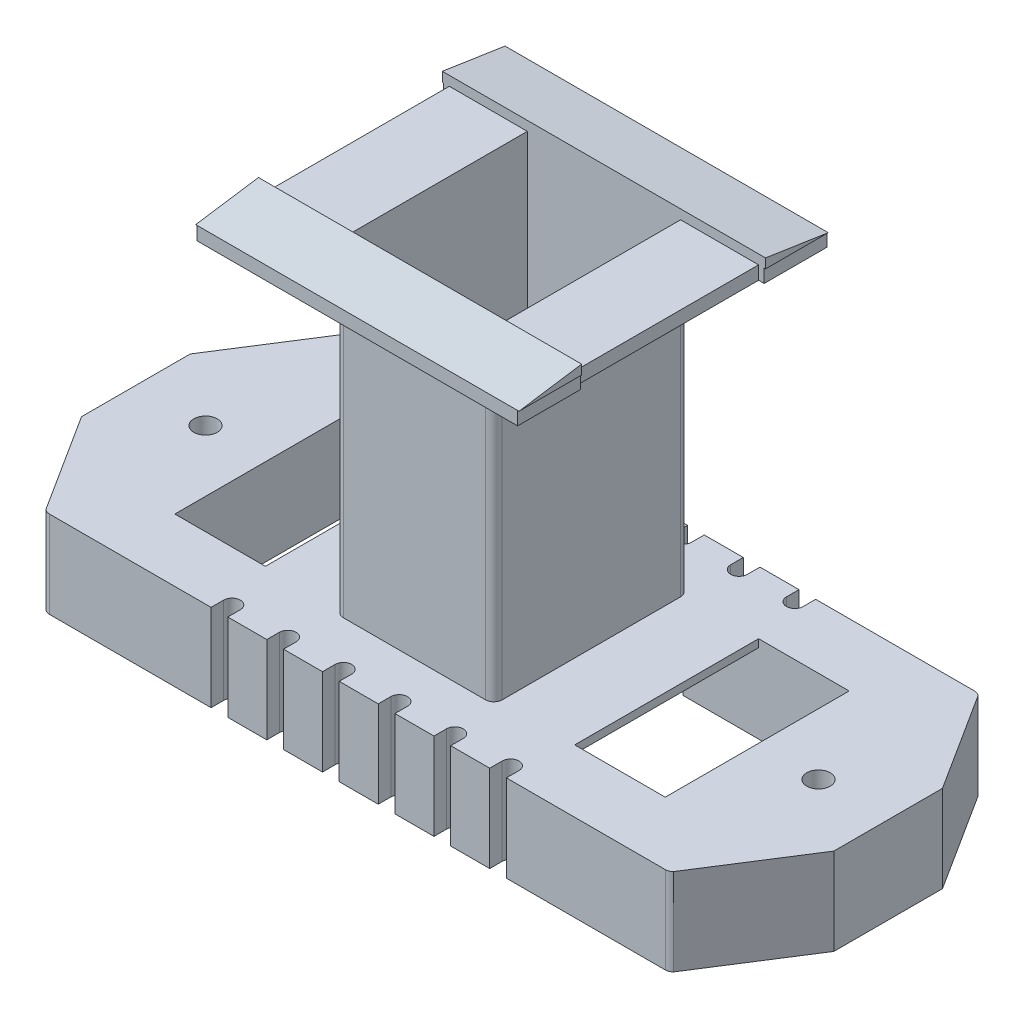
SolidWorks part; units mm, degrees
material "ABS"
ref_plane "Front Plane" through (0, 0, 0) normal (0, 0, 1) x (1, 0, 0)
ref_plane "Top Plane" through (0, 0, 0) normal (0, 1, 0) x (1, 0, 0)
ref_plane "Right Plane" through (0, 0, 0) normal (1, 0, 0) x (0, 0, -1)
sketch "Sketch2" plane through (0, 0, 0) normal (0, 1, 0) x (1, 0, 0)
  line L0 (14.25, -17.5) -> (14.25, 17.5)
  line L5 (13.25, -16.5) -> (-13.25, -16.5)
  line L6 (13.25, -16.5) -> (13.25, 16.5)
  line L11 (13.25, 16.5) -> (-13.25, 16.5)
  line L12 (-13.25, -16.5) -> (-13.25, 16.5)
  line L13 (13.25, -16.5) -> (-13.25, 16.5) construction
  line L14 (13.25, 16.5) -> (-13.25, -16.5) construction
  line L15 (14.25, 17.5) -> (-14.25, 17.5)
  line L16 (-14.25, -17.5) -> (-14.25, 17.5)
  line L17 (14.25, -17.5) -> (-14.25, -17.5)
  point P0 (0, 0)
  point P1 (0, 0)
  point P5 (0, 0)
  dimension "D1" = 33
  dimension "D2" = 26.5
  dimension "D3" = 1
extrude "Boss-Extrude1" add sketch "Sketch2" along normal mid plane 55.7
sketch "Sketch4" plane through (0, 27.85, 0) normal (0, 1, 0) x (1, 0, 0)
  line L1 (-28.75, -27.75) -> (28.75, -27.75)
  line L2 (-28.75, -27.75) -> (-28.75, 27.75)
  line L3 (-28.75, 27.75) -> (28.75, 27.75)
  line L4 (28.75, -27.75) -> (28.75, 27.75)
  line L5 (-28.75, -27.75) -> (28.75, 27.75) construction
  line L6 (-28.75, 27.75) -> (28.75, -27.75) construction
  line L14 (13.25, -16.5) -> (13.25, 16.5) construction
  line L15 (-13.25, -16.5) -> (13.25, -16.5) construction
  line L16 (-13.25, 16.5) -> (-13.25, -16.5) construction
  line L17 (13.25, 16.5) -> (-13.25, 16.5) construction
  line L18 (13.25, -16.5) -> (13.25, 16.5)
  line L19 (-13.25, -16.5) -> (13.25, -16.5)
  line L20 (-13.25, 16.5) -> (-13.25, -16.5)
  line L21 (13.25, 16.5) -> (-13.25, 16.5)
  point P0 (0, 0)
  dimension "D1" = 57.5
  dimension "D2" = 55.5
extrude "Boss-Extrude2" add sketch "Sketch4" along normal blind 2.4
mirror "Mirror1" about plane through (0, 0, 0) normal (0, 1, 0) of "Boss-Extrude2"
fillet "Fillet1" radius 1.5 4 edges at (-14.25, 0, 17.5) (-14.25, 0, -17.5) (14.25, 0, -17.5) (14.25, 0, 17.5)
sketch "Sketch5" plane through (0, 0, 0) normal (1, 0, 0) x (0, 0, -1)
  line L0 (-27.75, 30.25) -> (-16.5, 31.95)
  line L1 (-16.5, 31.95) -> (-16.5, 30.25)
  line L2 (-27.75, 30.25) -> (27.75, 30.25) construction
  line L4 (-16.5, 30.25) -> (-27.75, 30.25)
  line L5 (0, 0) -> (0, 38.1311) construction
  line L7 (27.75, 30.25) -> (16.5, 31.95)
  line L8 (16.5, 30.25) -> (27.75, 30.25)
  line L10 (-16.5, 30.25) -> (-16.5, -30.25) construction
  line L11 (16.5, 31.95) -> (16.5, 30.25)
  dimension "D1" = 1.7
extrude "Boss-Extrude3" add sketch "Sketch5" along normal mid plane 58
sketch "Sketch9" plane through (0, 33.6744, -5.0886) normal (0, 0.9888, -0.1494) x (1, 0, 0)
  line L0 (-29, 16.041) -> (29, 16.041) construction
  line L3 (29, 22.9187) -> (29, 11.541) construction
  line L4 (29, 11.541) -> (-29, 11.541) construction
  line L5 (-29, 22.9187) -> (-29, 11.541) construction
  text T0 "E85A" font "Century Gothic" height 4
  dimension "D1" = 4.5
extrude "Cut-Extrude2" [suppressed] cut sketch "Sketch9" against normal blind 0.01
sketch "Sketch8" plane through (0, -30.25, 0) normal (0, -1, 0) x (1, 0, 0)
  line L1 (-28.75, -27.75) -> (28.75, -27.75)
  line L2 (28.75, -27.75) -> (28.75, -16.5)
  line L37 (28.75, -16.5) -> (-28.75, -16.5)
  line L42 (-28.75, -16.5) -> (-28.75, -27.75)
  line L58 (0, 0) -> (37.0568, 0) construction
  line L79 (-28.75, 16.5) -> (-28.75, 27.75)
  line L82 (28.75, 16.5) -> (-28.75, 16.5)
  line L83 (28.75, 27.75) -> (28.75, 16.5)
  line L84 (-28.75, 27.75) -> (28.75, 27.75)
extrude "Boss-Extrude4" add sketch "Sketch8" along normal blind 13.2
sketch "Sketch11" plane through (0, -43.45, 0) normal (0, -1, 0) x (1, 0, 0)
  line L0 (0, 8.5975) -> (0, -6.374) construction
  line L3 (0, 0) -> (9.2559, 0) construction
  line L4 (28.75, 16.5) -> (44, 16.5)
  line L5 (28.75, -16.5) -> (44, -16.5)
  line L6 (44, 16.5) -> (44, -16.5)
  line L7 (28.75, 27.75) -> (28.75, 16.5)
  line L8 (13.25, 16.5) -> (28.75, 16.5) construction
  line L11 (28.75, -27.75) -> (28.75, -16.5)
  line L21 (28.75, 27.75) -> (55.25, 27.75)
  line L22 (56.75, 26.25) -> (56.75, 11.25) construction
  line L23 (58.25, 9.75) -> (67.5, 9.75) construction
  line L24 (67.5, -9.75) -> (67.5, 9.75)
  line L25 (58.25, -9.75) -> (67.5, -9.75) construction
  line L26 (56.75, -26.25) -> (56.75, -11.25) construction
  line L27 (28.75, -27.75) -> (55.25, -27.75)
  line L30 (-28.75, -27.75) -> (-55.25, -27.75)
  line L31 (-56.75, -26.25) -> (-56.75, -11.25) construction
  line L32 (-58.25, -9.75) -> (-67.5, -9.75) construction
  line L33 (-67.5, -9.75) -> (-67.5, 9.75)
  line L34 (-58.25, 9.75) -> (-67.5, 9.75) construction
  line L35 (-56.75, 26.25) -> (-56.75, 11.25) construction
  line L36 (-28.75, 27.75) -> (-55.25, 27.75)
  line L37 (-28.75, -27.75) -> (-28.75, -16.5)
  line L40 (-28.75, 27.75) -> (-28.75, 16.5)
  line L41 (-44, 16.5) -> (-44, -16.5)
  line L42 (-28.75, -16.5) -> (-44, -16.5)
  line L43 (-28.75, 16.5) -> (-44, 16.5)
  line L44 (56.3161, 27.3052) -> (67.5, 9.75)
  line L45 (56.3161, -27.3052) -> (67.5, -9.75)
  line L46 (-56.3161, -27.3052) -> (-67.5, -9.75)
  line L47 (-56.3161, 27.3052) -> (-67.5, 9.75)
  arc A0 (56.6569, 26.7703) -> (56.3161, 27.3052) centre (55.25, 26.25) ccw construction
  arc A1 (56.3161, 27.3052) -> (55.25, 27.75) centre (55.25, 26.25) ccw
  circle A3 centre (55, 0) radius 2.1
  arc A8 (55.25, -27.75) -> (56.3161, -27.3052) centre (55.25, -26.25) ccw
  arc A9 (56.75, -11.25) -> (58.25, -9.75) centre (58.25, -11.25) cw construction
  arc A10 (56.75, 26.25) -> (56.6569, 26.7703) centre (55.25, 26.25) ccw construction
  arc A11 (56.75, 11.25) -> (58.25, 9.75) centre (58.25, 11.25) ccw construction
  arc A14 (-56.75, 11.25) -> (-58.25, 9.75) centre (-58.25, 11.25) cw construction
  arc A15 (-56.3161, 27.3052) -> (-55.25, 27.75) centre (-55.25, 26.25) cw
  arc A16 (-56.75, -11.25) -> (-58.25, -9.75) centre (-58.25, -11.25) ccw construction
  arc A17 (-55.25, -27.75) -> (-56.3161, -27.3052) centre (-55.25, -26.25) cw
  circle A18 centre (-55, 0) radius 2.1
  arc A19 (56.3161, -27.3052) -> (56.6569, -26.7703) centre (55.25, -26.25) ccw construction
  arc A20 (56.6569, -26.7703) -> (56.75, -26.25) centre (55.25, -26.25) ccw construction
  arc A21 (-56.75, 26.25) -> (-56.6569, 26.7703) centre (-55.25, 26.25) cw construction
  arc A22 (-56.6569, 26.7703) -> (-56.3161, 27.3052) centre (-55.25, 26.25) cw construction
  arc A23 (-56.3161, -27.3052) -> (-56.6569, -26.7703) centre (-55.25, -26.25) cw construction
  arc A24 (-56.6569, -26.7703) -> (-56.75, -26.25) centre (-55.25, -26.25) cw construction
  point P48 (67.5, 0)
  point P52 (56.75, -27.75)
  point P55 (56.75, -9.75)
  point P58 (56.75, 27.75)
  point P61 (56.75, 9.75)
  point P76 (-56.75, 9.75)
  point P77 (-56.75, 27.75)
  point P78 (-56.75, -9.75)
  point P79 (-56.75, -27.75)
  point P80 (-67.5, 0)
  dimension "D1" = 55
  dimension "D3" = 4.2
  dimension "D7" = 28
  dimension "D9" = 1.5
  dimension "D2" = 23.5
  dimension "D4" = 44
  dimension "D5" = 212.5
  dimension "D8" = 18
extrude "Boss-Extrude5" add sketch "Sketch11" against normal up to surface (15.6 mm away) up to face at (0, -27.85, 0)
sketch "Sketch7" plane through (0, -30.25, 0) normal (0, -1, 0) x (1, 0, 0)
  line L0 (0, 0) -> (0, 58.3367) construction
  line L2 (-28.75, -16.5) -> (-28.75, 16.5) construction
  line L7 (0, 0) -> (-44.9899, 0) construction
  line L23 (-29, 28) -> (29, 28) construction
  line L24 (-26.25, 25.5) -> (-26.25, 28)
  line L25 (-26.25, -25.5) -> (-26.25, -28)
  line L26 (-26.25, 28) -> (-23.25, 28)
  line L27 (-26.25, -28) -> (-23.25, -28)
  line L28 (-23.25, 28) -> (-23.25, 25.5)
  line L29 (-23.25, -28) -> (-23.25, -25.5)
  line L31 (-16.25, 25.5) -> (-16.25, 28)
  line L32 (-16.25, 28) -> (-13.25, 28)
  line L33 (-13.25, 28) -> (-13.25, 25.5)
  line L34 (-6.25, 25.5) -> (-6.25, 28)
  line L35 (-6.25, 28) -> (-3.25, 28)
  line L36 (-3.25, 28) -> (-3.25, 25.5)
  line L37 (3.75, 25.5) -> (3.75, 28)
  line L38 (3.75, 28) -> (6.75, 28)
  line L39 (6.75, 28) -> (6.75, 25.5)
  line L40 (13.75, 25.5) -> (13.75, 28)
  line L41 (13.75, 28) -> (16.75, 28)
  line L42 (16.75, 28) -> (16.75, 25.5)
  line L43 (23.75, 25.5) -> (23.75, 28)
  line L44 (23.75, 28) -> (26.75, 28)
  line L45 (26.75, 28) -> (26.75, 25.5)
  line L46 (-16.25, -25.5) -> (-16.25, -28)
  line L47 (-13.25, -28) -> (-13.25, -25.5)
  line L48 (-16.25, -28) -> (-13.25, -28)
  line L49 (-6.25, -25.5) -> (-6.25, -28)
  line L50 (-3.25, -28) -> (-3.25, -25.5)
  line L51 (-6.25, -28) -> (-3.25, -28)
  line L52 (3.75, -25.5) -> (3.75, -28)
  line L53 (6.75, -28) -> (6.75, -25.5)
  line L54 (3.75, -28) -> (6.75, -28)
  line L55 (13.75, -25.5) -> (13.75, -28)
  line L56 (16.75, -28) -> (16.75, -25.5)
  line L57 (13.75, -28) -> (16.75, -28)
  line L58 (23.75, -25.5) -> (23.75, -28)
  line L59 (26.75, -28) -> (26.75, -25.5)
  line L60 (23.75, -28) -> (26.75, -28)
  arc A0 (-26.25, 25.5) -> (-23.25, 25.5) centre (-24.75, 25.5) ccw
  arc A1 (-16.25, 25.5) -> (-13.25, 25.5) centre (-14.75, 25.5) ccw
  arc A2 (-6.25, 25.5) -> (-3.25, 25.5) centre (-4.75, 25.5) ccw
  arc A3 (3.75, 25.5) -> (6.75, 25.5) centre (5.25, 25.5) ccw
  arc A4 (13.75, 25.5) -> (16.75, 25.5) centre (15.25, 25.5) ccw
  arc A5 (23.75, 25.5) -> (26.75, 25.5) centre (25.25, 25.5) ccw
  arc A6 (23.75, -25.5) -> (26.75, -25.5) centre (25.25, -25.5) cw
  arc A7 (13.75, -25.5) -> (16.75, -25.5) centre (15.25, -25.5) cw
  arc A8 (3.75, -25.5) -> (6.75, -25.5) centre (5.25, -25.5) cw
  arc A9 (-6.25, -25.5) -> (-3.25, -25.5) centre (-4.75, -25.5) cw
  arc A10 (-16.25, -25.5) -> (-13.25, -25.5) centre (-14.75, -25.5) cw
  arc A11 (-26.25, -25.5) -> (-23.25, -25.5) centre (-24.75, -25.5) cw
  arc A12 (-23.25, 25.5) -> (-26.25, 25.5) centre (-24.75, 25.5) ccw construction
  arc A13 (-13.25, 25.5) -> (-16.25, 25.5) centre (-14.75, 25.5) ccw construction
  arc A14 (-3.25, 25.5) -> (-6.25, 25.5) centre (-4.75, 25.5) ccw construction
  arc A15 (6.75, 25.5) -> (3.75, 25.5) centre (5.25, 25.5) ccw construction
  arc A16 (16.75, 25.5) -> (13.75, 25.5) centre (15.25, 25.5) ccw construction
  arc A17 (26.75, 25.5) -> (23.75, 25.5) centre (25.25, 25.5) ccw construction
  arc A18 (-23.25, -25.5) -> (-26.25, -25.5) centre (-24.75, -25.5) cw construction
  arc A19 (-13.25, -25.5) -> (-16.25, -25.5) centre (-14.75, -25.5) cw construction
  arc A20 (-3.25, -25.5) -> (-6.25, -25.5) centre (-4.75, -25.5) cw construction
  arc A21 (6.75, -25.5) -> (3.75, -25.5) centre (5.25, -25.5) cw construction
  arc A22 (16.75, -25.5) -> (13.75, -25.5) centre (15.25, -25.5) cw construction
  arc A23 (26.75, -25.5) -> (23.75, -25.5) centre (25.25, -25.5) cw construction
  dimension "D1" = 3
  dimension "D6" = 6
  dimension "D2" = 4
  dimension "D3" = 2.5
  dimension "D4" = 6
  dimension "D5" = 2.5
  dimension "D7" = 6
extrude "Cut-Extrude1" cut sketch "Sketch7" against normal mid plane 33
sketch "Sketch12" plane through (0, -30.25, 0) normal (0, -1, 0) x (1, 0, 0)
  line L0 (-44, 16.5) -> (44, 16.5) construction
  line L1 (-13.75, -16.5) -> (13.75, -16.5)
  line L2 (-13.75, -16.5) -> (-13.75, 16.5)
  line L3 (-13.75, 16.5) -> (13.75, 16.5)
  line L4 (13.75, -16.5) -> (13.75, 16.5)
  line L5 (-13.75, -16.5) -> (13.75, 16.5) construction
  line L6 (-13.75, 16.5) -> (13.75, -16.5) construction
  line L7 (-13.25, -16.5) -> (-13.25, 16.5) construction
  line L8 (44, -16.5) -> (-44, -16.5) construction
  line L9 (-42.75, 16.5) -> (-27.75, 16.5)
  line L10 (-42.75, 16.5) -> (-42.75, -16.5)
  line L11 (-42.75, -16.5) -> (-27.75, -16.5)
  line L12 (-27.75, 16.5) -> (-27.75, -16.5)
  line L13 (-42.75, 16.5) -> (-27.75, -16.5) construction
  line L14 (-42.75, -16.5) -> (-27.75, 16.5) construction
  line L15 (-28.75, -16.5) -> (-28.75, 16.5) construction
  line L16 (0, 0) -> (0, 36.2916) construction
  line L17 (42.75, -16.5) -> (27.75, -16.5)
  line L18 (27.75, 16.5) -> (27.75, -16.5)
  line L19 (42.75, 16.5) -> (27.75, 16.5)
  line L20 (42.75, 16.5) -> (42.75, -16.5)
  point P0 (0, 0)
  point P10 (-35.25, 0)
  dimension "D1" = 0.5
  dimension "D2" = 1
  dimension "D3" = 15
extrude "Cut-Extrude3" cut sketch "Sketch12" against normal through all both and the other way through all
sketch "Sketch14" plane through (0, -30.25, 0) normal (0, -1, 0) x (1, 0, 0)
  line L1 (-44, -16.5) -> (44, -16.5)
  line L2 (-44, -16.5) -> (-44, 16.5)
  line L3 (-44, 16.5) -> (44, 16.5)
  line L4 (44, -16.5) -> (44, 16.5)
  line L5 (-44, -16.5) -> (44, 16.5) construction
  line L6 (-44, 16.5) -> (44, -16.5) construction
  point P0 (0, 0)
extrude "Cut-Extrude4" cut sketch "Sketch14" against normal blind 1
sketch "Sketch15" plane through (0, -27.85, 0) normal (0, 1, 0) x (1, 0, 0)
  line L4 (-12.75, -17.5) -> (12.75, -17.5)
  line L5 (-14.25, 16) -> (-14.25, -16)
  line L6 (12.75, 17.5) -> (-12.75, 17.5)
  line L7 (14.25, -16) -> (14.25, 16)
  line L8 (-12.75, -17.5) -> (12.75, -17.5)
  line L9 (-14.25, 16) -> (-14.25, -16)
  line L10 (12.75, 17.5) -> (-12.75, 17.5)
  line L11 (14.25, -16) -> (14.25, 16)
  arc A4 (-14.25, -16) -> (-12.75, -17.5) centre (-12.75, -16) ccw
  arc A5 (-12.75, 17.5) -> (-14.25, 16) centre (-12.75, 16) ccw
  arc A6 (14.25, 16) -> (12.75, 17.5) centre (12.75, 16) ccw
  arc A7 (12.75, -17.5) -> (14.25, -16) centre (12.75, -16) ccw
  arc A8 (-14.25, -16) -> (-12.75, -17.5) centre (-12.75, -16) ccw
  arc A9 (-12.75, 17.5) -> (-14.25, 16) centre (-12.75, 16) ccw
  arc A10 (14.25, 16) -> (12.75, 17.5) centre (12.75, 16) ccw
  arc A11 (12.75, -17.5) -> (14.25, -16) centre (12.75, -16) ccw
  dimension "D1" = 0
extrude "Cut-Extrude5" cut sketch "Sketch15" against normal blind 40
sketch "Sketch18" plane through (0, -27.85, 0) normal (0, -1, 0) x (1, 0, 0)
  line L4 (12.75, 17.5) -> (-12.75, 17.5)
  line L5 (-14.25, 16) -> (-14.25, -16)
  line L6 (-12.75, -17.5) -> (12.75, -17.5)
  line L7 (14.25, -16) -> (14.25, 16)
  line L8 (12.75, 17.5) -> (-12.75, 17.5)
  line L9 (-14.25, 16) -> (-14.25, -16)
  line L10 (-12.75, -17.5) -> (12.75, -17.5)
  line L11 (14.25, -16) -> (14.25, 16)
  line L12 (-13.75, -16.5) -> (13.75, -16.5)
  line L13 (-13.75, 16.5) -> (-13.75, -16.5)
  line L14 (13.75, 16.5) -> (-13.75, 16.5)
  line L15 (13.75, -16.5) -> (13.75, 16.5)
  line L16 (-13.75, -16.5) -> (13.75, -16.5)
  line L17 (-13.75, 16.5) -> (-13.75, -16.5)
  line L18 (13.75, 16.5) -> (-13.75, 16.5)
  line L19 (13.75, -16.5) -> (13.75, 16.5)
  arc A4 (14.25, 16) -> (12.75, 17.5) centre (12.75, 16) ccw
  arc A5 (-12.75, 17.5) -> (-14.25, 16) centre (-12.75, 16) ccw
  arc A6 (-14.25, -16) -> (-12.75, -17.5) centre (-12.75, -16) ccw
  arc A7 (12.75, -17.5) -> (14.25, -16) centre (12.75, -16) ccw
  arc A8 (14.25, 16) -> (12.75, 17.5) centre (12.75, 16) ccw
  arc A9 (-12.75, 17.5) -> (-14.25, 16) centre (-12.75, 16) ccw
  arc A10 (-14.25, -16) -> (-12.75, -17.5) centre (-12.75, -16) ccw
  arc A11 (12.75, -17.5) -> (14.25, -16) centre (12.75, -16) ccw
  dimension "D1" = 0
  dimension "D2" = 0
extrude "Boss-Extrude6" add sketch "Sketch18" along normal blind 1.5
